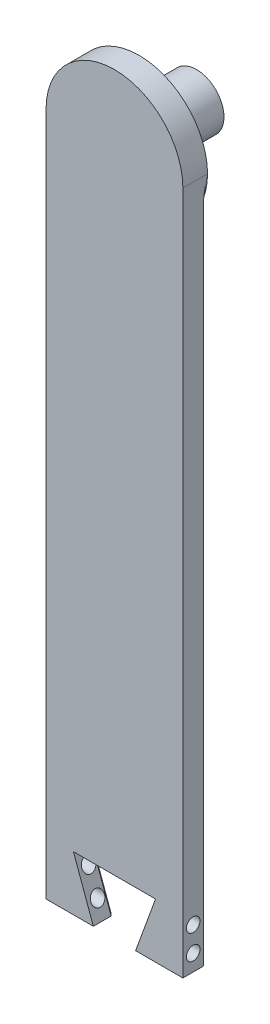
SolidWorks part; units mm, degrees
ref_plane "Front Plane" through (0, 0, 0) normal (0, 0, 1) x (1, 0, 0)
ref_plane "Top Plane" through (0, 0, 0) normal (0, 1, 0) x (1, 0, 0)
ref_plane "Right Plane" through (0, 0, 0) normal (1, 0, 0) x (0, 0, -1)
sketch "Sketch2" plane through (0, 0, 0) normal (0, 0, 1) x (1, 0, 0)
  line L0 (0, 0) -> (0, -250) construction
  line L1 (25, 0) -> (25, -250)
  line L2 (-25, 0) -> (-25, -250)
  arc A0 (25, 0) -> (-25, 0) centre (0, 0) ccw
  arc A1 (-25, -250) -> (25, -250) centre (0, -250) ccw
  point P3 (0, -125)
  dimension "D1" = 25
  dimension "D2" = 250
extrude "Boss-Extrude1" add sketch "Sketch2" along normal mid plane 10
sketch "Sketch3" plane through (0, 0, -5) normal (0, 0, -1) x (-1, 0, 0)
  circle A0 centre (0, 0) radius 10
  dimension "D1" = 20
extrude "Boss-Extrude2" add sketch "Sketch3" along normal blind 20
sketch "Sketch4" plane through (0, 0, -25) normal (0, 0, -1) x (-1, 0, 0)
  line L0 (2.5, 1.6583) -> (2.5, -1.6583)
  arc A0 (2.5, 1.6583) -> (2.5, -1.6583) centre (0, 0) ccw
  dimension "D1" = 6
  dimension "D2" = 2.5
extrude "Cut-Extrude1" cut sketch "Sketch4" against normal blind 10
sketch "Sketch6" plane through (0, 0, -5) normal (0, 0, -1) x (-1, 0, 0)
  line L2 (-25, 0) -> (-25, -250)
  line L3 (25, -250) -> (25, 0)
  line L4 (-25, 0) -> (-25, -250)
  line L5 (25, -250) -> (25, 0)
  arc A0 (-25, 0) -> (25, 0) centre (0, 0) ccw
  arc A2 (25, 0) -> (-25, 0) centre (0, 0) ccw
  arc A3 (-25, -250) -> (25, -250) centre (0, -250) ccw
  arc A5 (-25, -250) -> (25, -250) centre (0, -250) ccw
  dimension "D1" = 0
extrude "Cut-Extrude3" cut sketch "Sketch6" against normal blind 2.5
fillet "Fillet1" radius 1.5 1 edges at (0, -25, -2.5)
sketch "Sketch7" plane through (0, 0, -5) normal (0, 0, -1) x (-1, 0, 0)
  circle A0 centre (0, 0) radius 25 construction
  circle A1 centre (0, 0) radius 25
  circle A2 centre (0, 0) radius 12
  dimension "D1" = 24
extrude "Cut-Extrude4" cut sketch "Sketch7" against normal blind 1
sketch "Sketch8" plane through (0, 0, 5) normal (0, 0, 1) x (1, 0, 0)
  line L0 (25, -250) -> (25, 0) construction
  line L1 (-25, -250) -> (25, -250)
  line L2 (-25, -250) -> (-25, -275)
  line L3 (-25, -275) -> (25, -275)
  line L4 (25, -250) -> (25, -275)
  arc A0 (-25, -250) -> (25, -250) centre (0, -250) ccw construction
  point P8 (0, 0)
extrude "Cut-Extrude5" cut sketch "Sketch8" against normal up to next
sketch "Sketch9" plane through (0, 0, 5) normal (0, 0, 1) x (1, 0, 0)
  line L0 (0, -1275) -> (0, 48725) construction
  line L1 (25, -250) -> (-25, -250) construction
  line L2 (-7.7206, -250) -> (-15, -230)
  line L3 (-15, -230) -> (15, -230)
  line L4 (15, -230) -> (7.7206, -250)
  line L6 (-7.7206, -250) -> (7.7206, -250)
  point P2 (12.0934, -262.6653)
  point P5 (10.1325, -275)
  point P10 (-0.5237, -275)
  point P11 (0, -250)
  point P12 (0, -250)
  point P13 (15, -262.418)
  dimension "D1" = 110
  dimension "D2" = 110
  dimension "D3" = 30
  dimension "D4" = 20
extrude "Cut-Extrude6" cut sketch "Sketch9" against normal up to next
sketch "Sketch10" plane through (-25, 0, 0) normal (-1, 0, 0) x (0, 0, 1)
  line L0 (5, -250) -> (-2.5, -250) construction
  line L1 (1.25, -244) -> (-2.5, -250) construction
  line L2 (1.25, -244) -> (5, -250) construction
  circle A0 centre (1.25, -244) radius 2.5
  circle A1 centre (1.25, -235) radius 2.5
  dimension "D2" = 5
  dimension "D1" = 6
  dimension "D3" = 9
extrude "Cut-Extrude7" cut sketch "Sketch10" against normal through all
chamfer "Chamfer1" distance 1 angle 45 1 edges at (-12, 0, -5)
fillet "Fillet2" radius 1 1 edges at (10, 0, -5)
chamfer "Chamfer2" distance 1 angle 45 3 edges at (-11.3603, -240, -2.5) (0, -230, -2.5) (11.3603, -240, -2.5)
